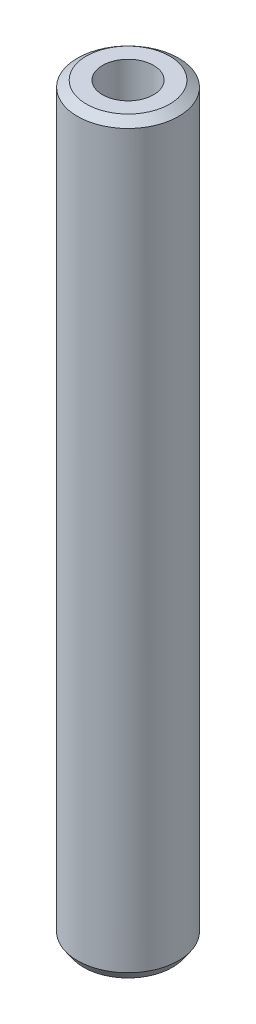
SolidWorks part; units mm, degrees
ref_plane "Front Plane" through (0, 0, 0) normal (0, 0, 1) x (1, 0, 0)
ref_plane "Top Plane" through (0, 0, 0) normal (0, 1, 0) x (1, 0, 0)
ref_plane "Right Plane" through (0, 0, 0) normal (1, 0, 0) x (0, 0, -1)
sketch "Sketch1" plane through (0, 0, 0) normal (0, 1, 0) x (1, 0, 0)
  circle A0 centre (0, 0) radius 5
  dimension "SHAFT_OD" = 10
extrude "Boss-Extrude1" add sketch "Sketch1" along normal blind 73.8165
sketch "Sketch2" plane through (0, 0, 0) normal (0, 1, 0) x (1, 0, 0)
  circle A0 centre (0, 0) radius 2.5226
  dimension "BORE_D" = 5.0452
extrude "Cut-Extrude1" cut sketch "Sketch2" along normal through all
chamfer "Chamfer1" distance 0.6132 angle 55.165 2 edges at (0, 73.8165, 5) (0, 0, 5) first distance on face at (0, 73.8165, 5) first distance on face at (0, 0, 2.5226)
